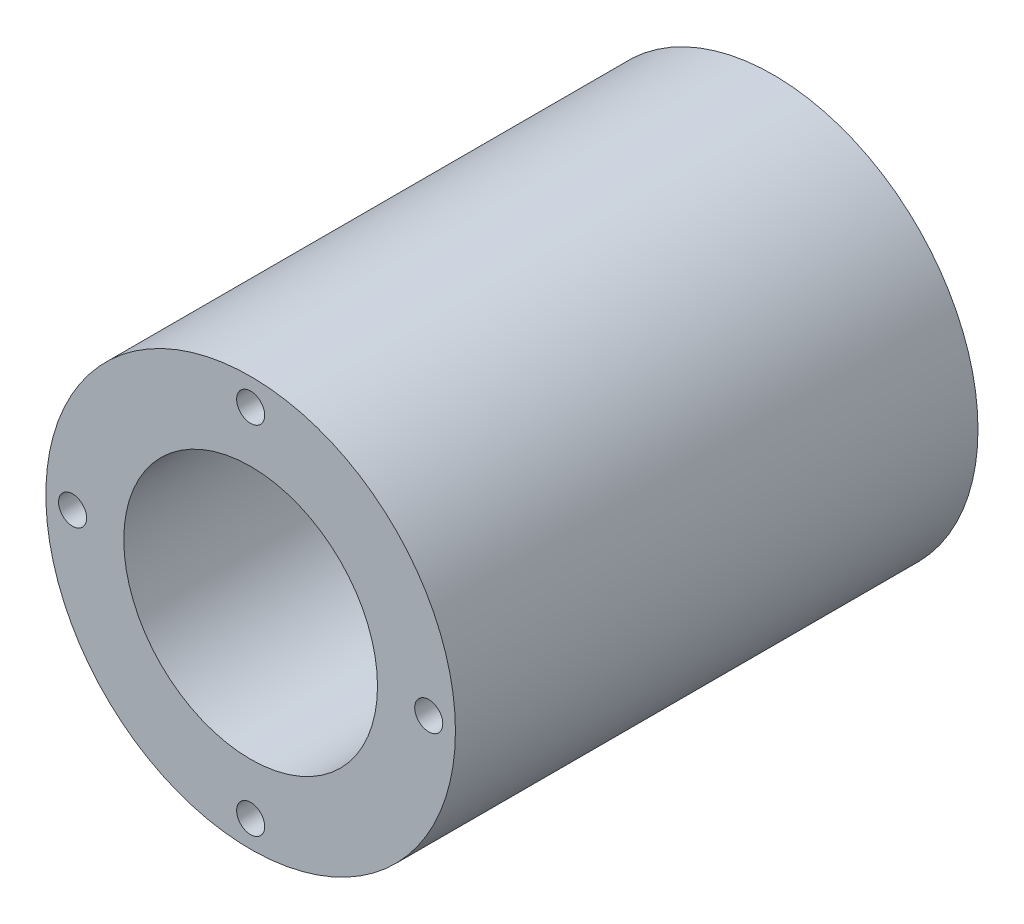
SolidWorks part; units mm, degrees
material "6061-T6 (SS)"
ref_plane "Front Plane" through (0, 0, 0) normal (0, 0, 1) x (1, 0, 0)
ref_plane "Top Plane" through (0, 0, 0) normal (0, 1, 0) x (1, 0, 0)
ref_plane "Right Plane" through (0, 0, 0) normal (1, 0, 0) x (0, 0, -1)
sketch "Sketch Spindle Skeleton" plane through (0, 0, 0) normal (1, 0, 0) x (0, 0, -1)
  line L0 (-95.847, -9.525) -> (-140.95, -9.525)
  line L5 (-1000, 0) -> (49000, 0)
  line L6 (0, -9.525) -> (0, 9.525)
  line L13 (0, 9.525) -> (-45.847, 9.525)
  line L26 (-45.847, 9.525) -> (-45.847, 14)
  line L27 (-45.847, 14) -> (-95.847, 14)
  line L32 (-95.847, 14) -> (-95.847, 9.525)
  line L34 (-160, 7) -> (-160, -7)
  line L36 (-95.847, -9.525) -> (-95.847, -14)
  line L37 (-95.847, -14) -> (-45.847, -14)
  line L38 (-45.847, -14) -> (-45.847, -9.525)
  line L39 (0, -9.525) -> (-45.847, -9.525)
  line L40 (-25.305, 36.5125) -> (-16.305, 36.5125)
  line L41 (-111.341, 22.6187) -> (-95.847, 22.6187)
  line L42 (-111.341, 22.6187) -> (-111.341, -22.6187)
  line L43 (-111.341, -22.6187) -> (-95.847, -22.6187)
  line L44 (-95.847, 22.6187) -> (-95.847, -22.6187)
  line L45 (-111.341, 22.6187) -> (-95.847, -22.6187) construction
  line L46 (-111.341, -22.6187) -> (-95.847, 22.6187) construction
  line L47 (-30.353, 22.6187) -> (-45.847, 22.6187)
  line L48 (-30.353, 22.6187) -> (-30.353, -22.6187)
  line L49 (-30.353, -22.6187) -> (-45.847, -22.6187)
  line L50 (-45.847, 22.6187) -> (-45.847, -22.6187)
  line L51 (-30.353, 22.6187) -> (-45.847, -22.6187) construction
  line L52 (-30.353, -22.6187) -> (-45.847, 22.6187) construction
  line L59 (-16.305, 36.5125) -> (-16.305, -36.5125)
  line L60 (-16.305, -36.5125) -> (-25.305, -36.5125)
  line L61 (-25.305, -22.6187) -> (-27.305, -22.6187)
  line L62 (-27.305, -22.6187) -> (-27.305, -12.5)
  line L63 (-27.305, -12.5) -> (-25.305, -12.5)
  line L64 (-25.305, -12.5) -> (-25.305, 12.5)
  line L65 (-25.305, 12.5) -> (-27.305, 12.5)
  line L66 (-27.305, 12.5) -> (-27.305, 22.6187)
  line L67 (-27.305, 22.6187) -> (-25.305, 22.6187)
  line L68 (-25.305, 22.6187) -> (-25.305, 36.5125)
  line L69 (-25.305, -22.6187) -> (-25.305, -36.5125)
  line L71 (-119.469, 36.5125) -> (-26.305, 36.5125)
  line L72 (-119.469, 36.5125) -> (-119.469, -36.5125)
  line L73 (-119.469, -36.5125) -> (-26.305, -36.5125)
  line L74 (-26.305, 36.5125) -> (-26.305, -36.5125)
  line L75 (-119.469, 36.5125) -> (-26.305, -36.5125) construction
  line L76 (-119.469, -36.5125) -> (-26.305, 36.5125) construction
  line L77 (-140.95, -9.525) -> (-140.95, -7)
  line L78 (-140.95, -7) -> (-160, -7)
  line L79 (-95.847, 9.525) -> (-140.95, 9.525)
  line L80 (-140.95, 7) -> (-160, 7)
  line L81 (-140.95, 9.525) -> (-140.95, 7)
  line L82 (-118.3985, 9.525) -> (-118.3985, -9.525) construction
  line L83 (-22.9235, 9.525) -> (-22.9235, -9.525) construction
  line L96 (-119.469, 36.5125) -> (-134.709, 36.5125)
  line L98 (-119.469, -36.5125) -> (-134.709, -36.5125)
  line L99 (-134.709, 36.5125) -> (-134.709, -36.5125)
  line L110 (-119.469, 36.5125) -> (-119.469, -36.5125)
  point P3 (0, 0)
  point P18 (-103.594, 0)
  point P24 (-38.1, 0)
  point P29 (-72.887, 0)
  point P48 (-16.305, 30.5656)
  point P70 (-134.709, 31.75)
sketch "Sketch1" plane through (0, 0, 0) normal (1, 0, 0) x (0, 0, -1)
  line L0 (-26.305, 36.5125) -> (-26.305, -36.5125) construction
  line L1 (-119.469, -36.5125) -> (-26.305, -36.5125) construction
  line L2 (-119.469, 36.5125) -> (-119.469, -36.5125) construction
  line L3 (-119.469, 36.5125) -> (-26.305, 36.5125) construction
  line L4 (-26.305, 36.5125) -> (-26.305, -36.5125)
  line L5 (-119.469, -36.5125) -> (-26.305, -36.5125)
  line L6 (-119.469, 36.5125) -> (-119.469, -36.5125)
  line L7 (-119.469, 36.5125) -> (-26.305, 36.5125)
  line L9 (-30.353, 22.6187) -> (-45.847, 22.6187) construction
  line L10 (-119.469, 22.6187) -> (-26.305, 22.6187)
  line L15 (-119.469, 0) -> (-26.305, 0) construction
revolve "Revolve1" add sketch "Sketch1" angle 360 about L15 region at (0, 29.5656, 72.887)
sketch "Back Hole Top Location" plane through (0, 0, 26.305) normal (0, 0, -1) x (-1, 0, 0)
  point P9 (0, 30.5656)
hole_wizard "M6x1.0 Tapped Hole3" positions "Sketch8" profile "Sketch9" tap size "M6x1.0" standard "ANSI Metric"
sketch "Sketch8" plane through (0, 0, 26.305) normal (0, 0, -1) x (-1, 0, 0)
  point P0 (0, 30.5656)
sketch "Sketch9" plane through (0, 30.5656, 26.305) normal (1, 0, 0) x (0, 1, 0)
  line L0 (0, 0) -> (0, 16.5022)
  line L1 (0, 16.5022) -> (2.5, 15)
  line L2 (2.5, 15) -> (2.5, 0)
  line L5 (2.5, 0) -> (0, 0)
  line L10 (0, 16.5022) -> (-2.5, 15) construction
  line L11 (0, -6.35) -> (0, 107.95) construction
  dimension "Tap Drill Dia." = 5
  dimension "Tap Drill Depth" = 15
  dimension "Drill Angle" = 118
pattern_circular "BackFacePattern" count 6 over 360 about axis through (0, 0, 1000) along (0, 0, -1) of "M6x1.0 Tapped Hole3"
ref_plane "Midplane" through (0, 0, 72.887) normal (0, 0, -1) x (-1, 0, 0)
sketch "Front Hole Top Location" plane through (0, 0, 119.469) normal (0, 0, 1) x (1, 0, 0)
  point P0 (0, 31.75)
hole_wizard "M6x1.0 Tapped Hole2" positions "Sketch5" profile "Sketch6" tap size "M6x1.0" standard "ANSI Metric"
sketch "Sketch5" plane through (0, 0, 119.469) normal (0, 0, 1) x (1, 0, 0)
  point P0 (0, 31.75)
sketch "Sketch6" plane through (0, 31.75, 119.469) normal (1, 0, 0) x (0, -1, 0)
  line L0 (0, 0) -> (0, 16.5022)
  line L1 (0, 16.5022) -> (2.5, 15)
  line L2 (2.5, 15) -> (2.5, 0)
  line L5 (2.5, 0) -> (0, 0)
  line L10 (0, 16.5022) -> (-2.5, 15) construction
  line L11 (0, -6.35) -> (0, 107.95) construction
  dimension "Tap Drill Dia." = 5
  dimension "Tap Drill Depth" = 15
  dimension "Drill Angle" = 118
pattern_circular "FrontFacePattern" count 4 over 360 about axis through (0, 0, 1000) along (0, 0, -1) of "M6x1.0 Tapped Hole2"
sketch "Sketch7" plane through (0, 0, 26.305) normal (0, 0, -1) x (-1, 0, 0)
  circle A0 centre (0, 0) radius 26.9875
  circle A1 centre (0, 0) radius 24.6062
  dimension "D1" = 53.975
  dimension "D2" = 49.2125
extrude "Cut-Extrude1" [suppressed] cut sketch "Sketch7" against normal blind 0.5
